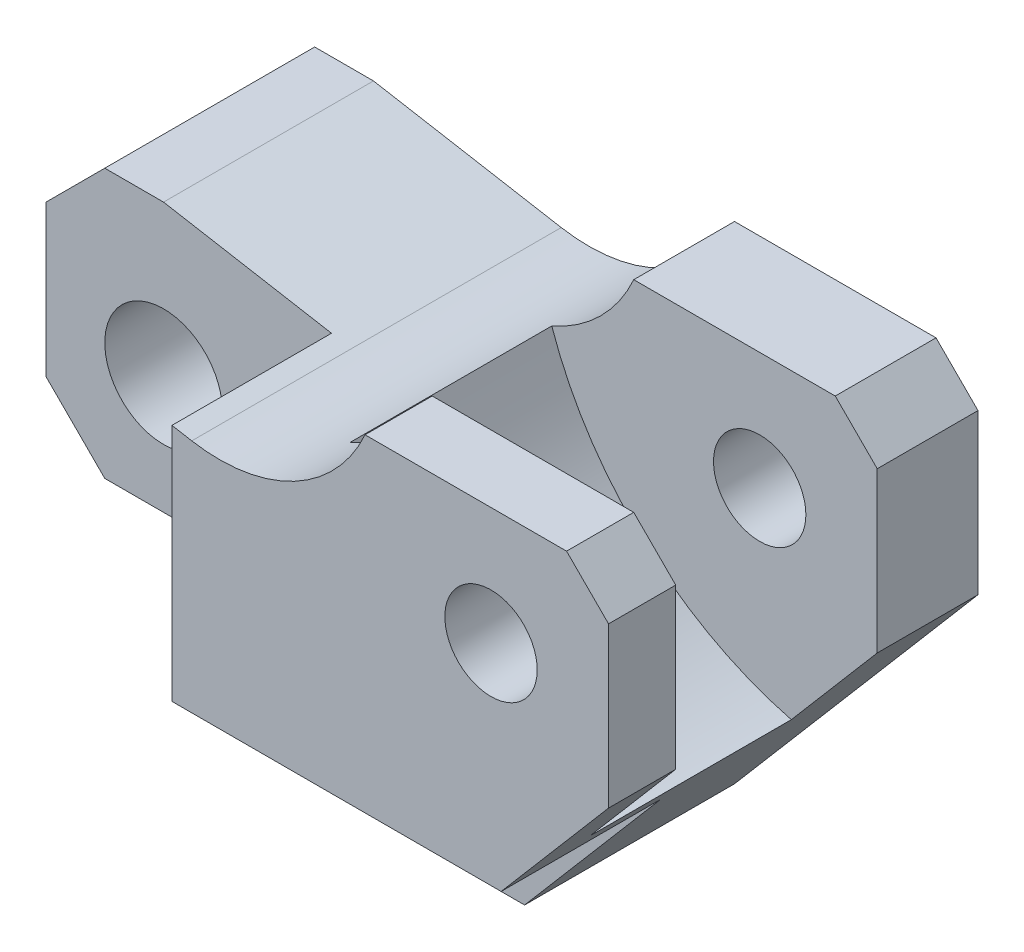
SolidWorks part; units mm, degrees
material "AISI 1020"
ref_plane "Front Plane" through (0, 0, 0) normal (0, 0, 1) x (1, 0, 0)
ref_plane "Top Plane" through (0, 0, 0) normal (0, 1, 0) x (1, 0, 0)
ref_plane "Right Plane" through (0, 0, 0) normal (1, 0, 0) x (0, 0, -1)
sketch "Sketch1" plane through (0, 0, 0) normal (0, 0, 1) x (1, 0, 0)
  line L0 (0, 0) -> (-7, 7)
  line L1 (-7, 7) -> (-7, 25)
  line L2 (-7, 25) -> (0, 32)
  line L6 (79, 34) -> (79, 15)
  line L7 (79, 15) -> (50, -19)
  line L8 (50, -19) -> (44.297, -19)
  line L9 (32.5755, 0) -> (0, 0)
  line L10 (79, 34) -> (74, 39)
  line L11 (74, 39) -> (50, 39)
  line L12 (0, 32) -> (7, 32)
  line L13 (7, 32) -> (29.3614, 28.0571)
  line L14 (7, -41.8607) -> (7, 32) construction
  line L15 (30.3211, 14) -> (-33.6507, 14) construction
  arc A2 (44.297, -19) -> (37.5212, -4.2647) centre (66.2059, 0) cw
  arc A4 (37.5212, -4.2647) -> (32.5755, 0) centre (32.5755, -5) ccw
  arc A5 (50, 39) -> (29.3614, 28.0571) centre (32.6607, 46.7684) cw
  circle A6 centre (7, 14) radius 7
  point P8 (47.1485, -19)
  point P20 (16.2878, 0)
  dimension "D5" = 29
  dimension "D6" = 5
  dimension "D14" = 19
  dimension "D21" = 14
  dimension "D2" = 7
  dimension "D3" = 45
  dimension "D4" = 19
  dimension "D7" = 29
  dimension "D8" = 19
  dimension "D9" = 24
  dimension "D10" = 45
  dimension "D11" = 5
  dimension "D12" = 29
  dimension "D13" = 58
  dimension "D15" = 10
  dimension "D17" = 32
  dimension "D16" = 45
  dimension "D18" = 86
  dimension "D19" = 14
  dimension "D20" = 14
extrude "Boss-Extrude1" add sketch "Sketch1" along normal mid plane 44
sketch "Sketch2" plane through (0, 0, 22) normal (0, 0, 1) x (1, 0, 0)
  line L0 (27, 0) -> (27, 28.4735)
  line L1 (0, 0) -> (32.5755, 0) construction
  line L2 (29.3614, 28.0571) -> (7, 32) construction
  line L3 (24.6138, 0) -> (27, 0)
  line L4 (50, -19) -> (79, 15) construction
  line L5 (79, 15) -> (79, 34) construction
  line L6 (74, 39) -> (50, 39) construction
  line L7 (44.297, -19) -> (50, -19) construction
  line L8 (-7, 7) -> (0, 0) construction
  line L9 (-7, 25) -> (-7, 7) construction
  line L10 (0, 32) -> (-7, 25) construction
  line L11 (7, 32) -> (0, 32) construction
  line L12 (50, -19) -> (66.2059, 0)
  line L13 (44.297, -19) -> (50, -19)
  line L14 (0, 0) -> (27, 0)
  line L15 (-7, 7) -> (0, 0)
  line L16 (-7, 25) -> (-7, 7)
  line L17 (0, 32) -> (-7, 25)
  line L18 (7, 32) -> (0, 32)
  line L19 (27, 28.4735) -> (7, 32)
  line L20 (32.5755, 0) -> (66.2059, 0)
  circle A0 centre (65, 25) radius 5.5
  arc A1 (37.5212, -4.2647) -> (32.5755, 0) centre (32.5755, -5) ccw construction
  arc A2 (37.5212, -4.2647) -> (44.297, -19) centre (66.2059, 0) ccw construction
  arc A3 (37.5212, -4.2647) -> (32.5755, 0) centre (32.5755, -5) ccw
  arc A4 (37.5212, -4.2647) -> (44.297, -19) centre (66.2059, 0) ccw
  line M3 (0, 0) -> (32.5755, 0)
  arc M4 (32.5755, 0) -> (37.5212, -4.2647) centre (32.5755, -5) cw
  arc M5 (37.5212, -4.2647) -> (44.297, -19) centre (66.2059, 0) ccw
  line M6 (44.297, -19) -> (50, -19)
  line M7 (50, -19) -> (79, 15)
  line M12 (29.3614, 28.0571) -> (7, 32)
  line M13 (7, 32) -> (0, 32)
  line M14 (0, 32) -> (-7, 25)
  line M15 (-7, 25) -> (-7, 7)
  line M16 (-7, 7) -> (0, 0)
  circle M17 centre (7, 14) radius 7
  dimension "D4" = 11
  dimension "D1" = 52
  dimension "D2" = 14
  dimension "D3" = 14
extrude "Cut-Extrude1" cut sketch "Sketch2" against normal blind 19 contours L0 M3 M12 M13 M14 M15 M16 M17 | L20 M4 M5 M6 M7 region at (25.8069, 0.4669, 22) region at (49.0899, -7.4639, 22)
extrude "Cut-Extrude2" cut sketch "Sketch2<3>" against normal through all contours A0
sketch "Sketch2<3>" plane through (0, 0, 22) normal (0, 0, 1) x (1, 0, 0) same geometry as "Sketch2"
sketch "Sketch3" plane through (0, 0, 0) normal (0, 0, 1) x (1, 0, 0)
  line L0 (66.2059, 0) -> (79, 15) construction
  line L1 (68.7647, 3) -> (79, 15)
  line L4 (74, 39) -> (50, 39) construction
  line L5 (79, 15) -> (79, 34) construction
  line L6 (79, 34) -> (74, 39) construction
  line L7 (79, 15) -> (79, 34)
  line L8 (79, 34) -> (74, 39)
  line L9 (74, 39) -> (50, 39)
  arc A1 (29.3614, 28.0571) -> (50, 39) centre (32.6607, 46.7684) ccw construction
  arc A2 (40.2369, 29.3443) -> (68.7647, 3) centre (79, 42.7019) ccw
  arc A3 (40.2369, 29.3443) -> (50, 39) centre (32.6607, 46.7684) ccw
  dimension "D1" = 36
  dimension "D2" = 41
extrude "Cut-Extrude3" cut sketch "Sketch3" against normal offset from surface 12 and the other way offset from surface 8 up to face at (70.5, 25, -22) other way up to face at (70.5, 25, 22)
equation "\"B\" = 58"
equation "\"A\" = 86"
equation "\"c\" = 44"
equation "\"D1@Boss-Extrude1\"=\"c\""
equation "\"D13@Sketch1\"=\"B\""
equation "\"D18@Sketch1\"=\"A\""
